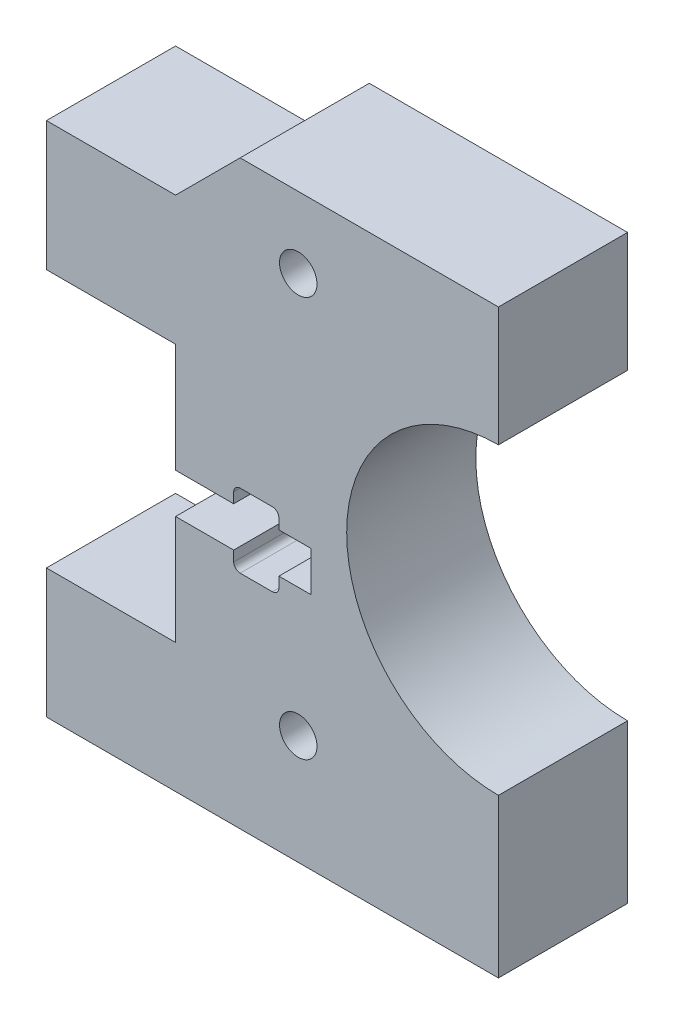
SolidWorks part; units mm, degrees
ref_plane "Front Plane" through (0, 0, 0) normal (0, 0, 1) x (1, 0, 0)
ref_plane "Top Plane" through (0, 0, 0) normal (0, 1, 0) x (1, 0, 0)
ref_plane "Right Plane" through (0, 0, 0) normal (1, 0, 0) x (0, 0, -1)
sketch "Sketch1" plane through (0, 0, 0) normal (0, 0, 1) x (1, 0, 0)
  line L0 (0, 0) -> (0, -50) construction
  line L1 (-10, -40) -> (0, -40) construction
  line L2 (25, -50) -> (25, 0) construction
  line L3 (25, 0) -> (0, 0) construction
  line L4 (0, 0) -> (0, -5)
  line L5 (0, -5) -> (-10, -5)
  line L6 (-10, -5) -> (-10, -15)
  line L7 (-10, -15) -> (0, -15)
  line L8 (0, -15) -> (0, -35)
  line L9 (25, -50) -> (0, -50) construction
  line L10 (0, -50) -> (25, -50)
  line L11 (-10, -35) -> (0, -35)
  line L12 (-10, -45) -> (-10, -35)
  line L13 (0, -45) -> (-10, -45)
  line L14 (25, -50) -> (25, 0)
  line L15 (0, 0) -> (25, 0)
  line L16 (0, -50) -> (0, -45)
  line L17 (-10, -10) -> (0, -10) construction
  line L18 (0, -25) -> (25, -25) construction
  dimension "D1" = 10
  dimension "D6" = 25
  dimension "D2" = 25
extrude "Boss-Extrude1" add sketch "Sketch1" along normal blind 10
sketch "Sketch2" plane through (0, 0, 10) normal (0, 0, 1) x (1, 0, 0)
  line L0 (25, -21) -> (0, -21) construction
  line L1 (25, -50) -> (25, 0) construction
  line L2 (0, -15) -> (0, -35) construction
  line L3 (25, -21) -> (9.5, -5.5) construction
  line L4 (25, -21) -> (9.5, -36.5) construction
  circle A0 centre (25, -21) radius 11.75
  circle A1 centre (9.5, -5.5) radius 1.45
  circle A2 centre (9.5, -36.5) radius 1.45
  point P6 (0, -25)
  dimension "D2" = 23.5
  dimension "D5" = 2.9
  dimension "D1" = 4
  dimension "D3" = 45
  dimension "D4" = 15.5
extrude "motor" cut sketch "Sketch2" against normal through all
sketch "Sketch3" plane through (0, 0, 10) normal (0, 0, 1) x (1, 0, 0)
  line L0 (0, -25) -> (10.5, -25) construction
  line L1 (0, -15) -> (0, -35) construction
  line L2 (10.5, -26.55) -> (10.5, -23.45) construction
  line L3 (10.5, -23.45) -> (0, -23.45) construction
  line L4 (0, -26.55) -> (0, -23.45)
  line L5 (0, -23.45) -> (4.5, -23.45)
  line L6 (4.5, -23.45) -> (4.5, -22.65)
  line L7 (5, -22.15) -> (7.5, -22.15)
  line L8 (8, -22.65) -> (8, -23.45)
  line L9 (8, -23.45) -> (10.5, -23.45)
  line L10 (10.5, -23.45) -> (10.5, -26.55)
  line L11 (10.5, -26.55) -> (0, -26.55) construction
  line L12 (8, -26.55) -> (10.5, -26.55)
  line L13 (8, -27.35) -> (8, -26.55)
  line L14 (5, -27.85) -> (7.5, -27.85)
  line L15 (4.5, -26.55) -> (4.5, -27.35)
  line L16 (0, -26.55) -> (4.5, -26.55)
  arc A0 (5, -27.85) -> (4.5, -27.35) centre (5, -27.35) cw
  arc A1 (8, -27.35) -> (7.5, -27.85) centre (7.5, -27.35) cw
  arc A2 (7.5, -22.15) -> (8, -22.65) centre (7.5, -22.65) cw
  arc A3 (4.5, -22.65) -> (5, -22.15) centre (5, -22.65) cw
  point P18 (4.5, -27.85)
  point P21 (8, -27.85)
  point P24 (8, -22.15)
  point P27 (4.5, -22.15)
  dimension "D6" = 0.5
  dimension "D1" = 1.55
  dimension "D2" = 8
  dimension "D3" = 10.5
  dimension "D4" = 2.85
  dimension "D5" = 3.5
extrude "screw" cut sketch "Sketch3" against normal through all
sketch "Sketch4" plane through (0, 0, 10) normal (0, 0, 1) x (1, 0, 0)
  line L0 (0, -45) -> (25, -45)
  line L1 (25, -50) -> (25, -32.75) construction
  line L2 (25, -45) -> (25, -50)
  line L3 (25, -50) -> (0, -50)
  line L4 (0, -50) -> (0, -45)
  line L5 (0, -5) -> (5, 0)
  line L6 (25, 0) -> (0, 0) construction
  line L7 (5, 0) -> (0, 0)
  line L8 (0, 0) -> (0, -5)
  dimension "D1" = 45
extrude "Cut-Extrude3" cut sketch "Sketch4" against normal through all
equation "\"X-ROD-SPACING\"=45"
equation "\"Y-ROD-SPACING\"=75"
equation "\"Z-ROD-SPACING\"=17.5"
equation "\"Y-BED-OFFSET\"=2"
equation "\"Y-BED-ROD-INSET\"=3.5"
equation "\"T-SLOT-NUT-FILLET-RADIUS\"=0.5"
equation "\"T-SLOT-SCREW-SHAFT-RADIUS\"=1.55"
equation "\"T-SLOT-SCREW-SHAFT-CUTOUT-LENGTH\"=11"
equation "\"T-SLOT-NUT-DEPTH\"=3.5"
equation "\"T-SLOT-NUT-WIDTH\"=2.85"
equation "\"T-SLOT-NUT-END-DISTANCE\"=8"
equation "\"ACRYLIC-THICKNESS\"=10"
equation "\"ACRYLIC-THICKNESS2\"=4.5"
equation "\"ACRYLIC-TAB-CUTOUT-SIZE\"=\"ACRYLIC-THICKNESS\"+\"ACRYLIC-TAB-TOLERANCE\"*2"
equation "\"ACRYLIC-TAB-WIDTH\"=\"ACRYLIC-THICKNESS\""
equation "\"ACRYLIC-M3-HOLE\"=2.9"
equation "\"SMOOTHROD-CAP-SCREW-DISTANCE\"=20"
equation "\"FRAME-WIDTH-INNER\"=370"
equation "\"NEMA17-HOLE-SPACING\"=31"
equation "\"NEMA17-CENTRAL-CUTOUT\"=22.5"
equation "\"Z-BRACKET-REACH\"=57"
equation "\"TOP-BRACKET-SPACING\"=40"
equation "\"SMOOTHROD-X-LENGTH\"=350"
equation "\"SMOOTHROD-Y-LENGTH\"=350"
equation "\"SMOOTHROD-Z-LENGTH\"=350"
equation "\"SMOOTHROD-TIGHTENING-HEADROOM\"=.25"
equation "\"LEADSCREW-Z-LENGTH\"=300"
equation "\"SCREW-LENGTH-FRAME\"=\"ACRYLIC-THICKNESS\" + 10"
equation "\"SCREW-HEAD-RADIUS\"=6"
equation "\"PRINTED-X-SMOOTHROD-DIAMETER\"=8.8"
equation "\"PRINTED-X-SMOOTHROD-CUTOUT\"=10"
equation "\"PRINTED-X-BASE-HEIGHT\"=10"
equation "\"PRINTED-LM8UU-CUTOUT-SIZE\"=15.5"
equation "\"PRINTED-LM8UU-CUTOUT-LENGTH\"=24.5"
equation "\"PRINTED-X-IDLER-HEIGHT\"=16"
equation "\"PSU-MOUNTING-WIDTH\"=95"
equation "\"PSU-MOUNTING-HEIGHT\"=177"
equation "\"D1@Sketch1\"=10"
equation "\"D3@Sketch1\"=10"
equation "\"D1@Boss-Extrude1\"=\"ACRYLIC-THICKNESS\""
equation "\"D2@Sketch2\"=\"NEMA17-CENTRAL-CUTOUT\"+1"
equation "\"D4@Sketch2\"=\"NEMA17-HOLE-SPACING\"/2"
equation "\"D5@Sketch2\"=\"ACRYLIC-M3-HOLE\""
equation "\"D1@Sketch3\"=\"T-SLOT-SCREW-SHAFT-RADIUS\""
equation "\"D4@Sketch3\"=\"T-SLOT-NUT-WIDTH\""
equation "\"D2@Sketch3\"=\"T-SLOT-NUT-END-DISTANCE\""
equation "\"D5@Sketch3\"=\"T-SLOT-NUT-DEPTH\""
equation "\"D6@Sketch3\"=\"T-SLOT-NUT-FILLET-RADIUS\""
